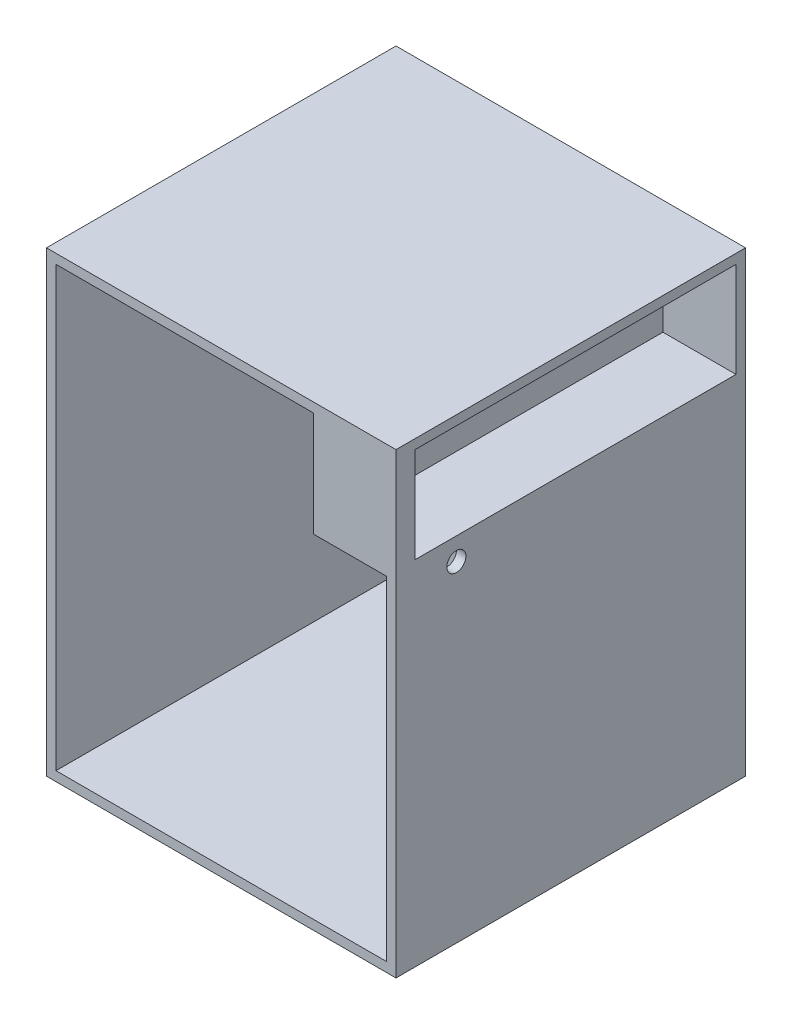
SolidWorks part; units mm, degrees
material "Balsa"
ref_plane "Alzado" through (0, 0, 0) normal (0, 0, 1) x (1, 0, 0)
ref_plane "Planta" through (0, 0, 0) normal (0, 1, 0) x (1, 0, 0)
ref_plane "Vista lateral" through (0, 0, 0) normal (1, 0, 0) x (0, 0, -1)
sketch "Croquis1" plane through (0, 0, 0) normal (0, 1, 0) x (1, 0, 0)
  line L1 (275, -275) -> (-275, -275)
  line L2 (275, -275) -> (275, 275)
  line L3 (275, 275) -> (-275, 275)
  line L4 (-275, -275) -> (-275, 275)
  line L5 (275, -275) -> (-275, 275) construction
  line L6 (275, 275) -> (-275, -275) construction
  point P0 (0, 0)
  dimension "D1" = 550
  dimension "D2" = 550
extrude "Saliente-Extruir1" add sketch "Croquis1" along normal blind 720
shell "Vaciado1" thickness 15 removed face at (0, 360, 275)
sketch "Croquis2" plane through (0, 0, 275) normal (0, 0, 1) x (1, 0, 0)
  line L11 (160, 705) -> (160, 555)
  line L17 (-260, 705) -> (260, 705) construction
  line L18 (160, 555) -> (260, 555)
  line L19 (260, 705) -> (260, 15) construction
  line L20 (145, 705) -> (145, 540)
  line L21 (145, 540) -> (260, 540)
  line L22 (145, 705) -> (160, 705)
  line L23 (260, 555) -> (260, 540)
  dimension "D1" = 100
  dimension "D2" = 150
  dimension "D3" = 15
extrude "Saliente-Extruir2" add sketch "Croquis2" against normal up to vertex (535 mm away) up to point (260, 705, -260)
sketch "Croquis3" plane through (275, 0, 0) normal (1, 0, 0) x (0, 0, -1)
  line L0 (-275, 705) -> (260, 705) construction
  line L1 (-245, 705) -> (260, 705)
  line L2 (-245, 705) -> (-245, 555)
  line L3 (-245, 555) -> (260, 555)
  line L4 (260, 705) -> (260, 555)
  line L5 (260, 555) -> (-275, 555) construction
  line L6 (260, 705) -> (260, 555) construction
  line L8 (-275, 720) -> (-275, 0) construction
  dimension "D1" = 30
extrude "Cortar-Extruir1" cut sketch "Croquis3" against normal up to surface (115 mm away) up to face at (160, 630, 7.5)
sketch "Croquis4" plane through (160, 0, 0) normal (1, 0, 0) x (0, 0, -1)
  line L1 (-275, 705) -> (-260, 705)
  line L2 (-275, 705) -> (-275, 555)
  line L3 (-275, 555) -> (-260, 555)
  line L4 (-260, 705) -> (-260, 555)
  dimension "D1" = 15
extrude "Saliente-Extruir3" add sketch "Croquis4" along normal up to vertex (100 mm away) up to point (260, 555, 275)
sketch "Croquis5" plane through (-275, 0, 0) normal (-1, 0, 0) x (0, 0, 1)
  line L1 (-275, 720) -> (-275, 0) construction
  line L2 (-275, 720) -> (275, 720) construction
  circle A0 centre (-180, 520) radius 15
  dimension "D2" = 30
  dimension "D1" = 95
  dimension "D3" = 200
extrude "Cortar-Extruir2" cut sketch "Croquis5" against normal blind 30
sketch "Croquis6" plane through (275, 0, 0) normal (1, 0, 0) x (0, 0, -1)
  line L0 (-275, 720) -> (-275, 0) construction
  line L1 (-275, 720) -> (275, 720) construction
  circle A0 centre (-180, 520) radius 15
  dimension "D3" = 30
  dimension "D1" = 95
  dimension "D2" = 200
extrude "Cortar-Extruir3" cut sketch "Croquis6" against normal blind 30
